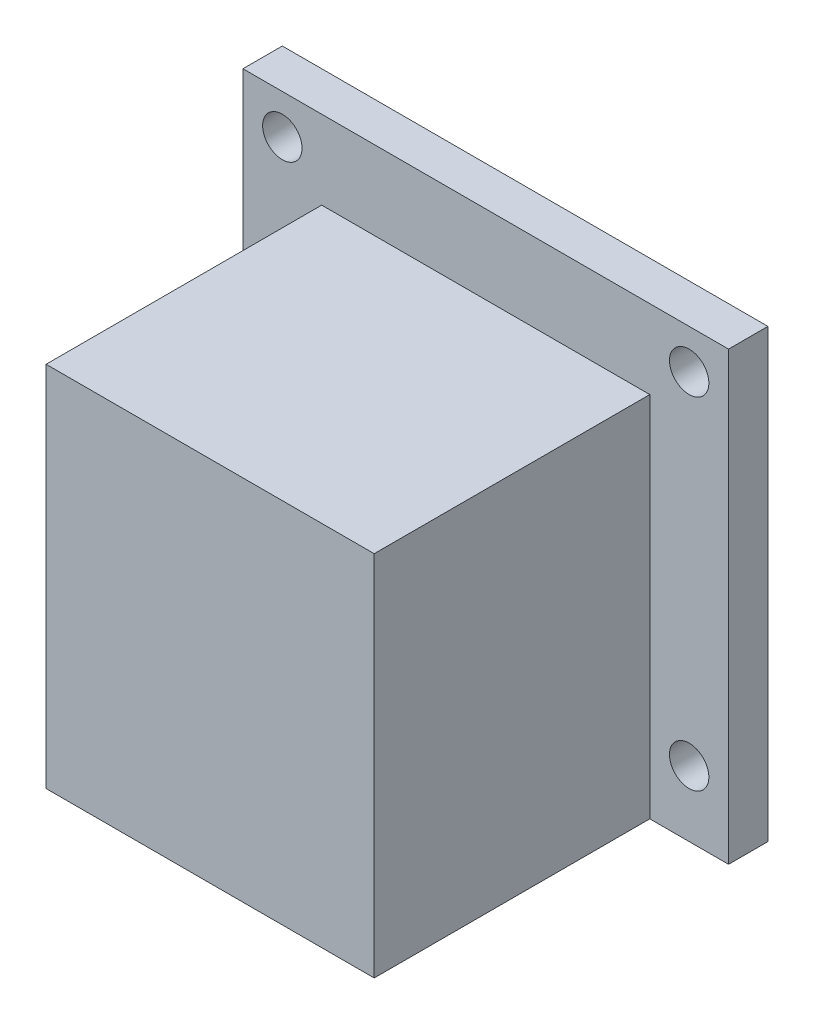
SolidWorks part; units mm, degrees
ref_plane "前视基准面" through (0, 0, 0) normal (0, 0, 1) x (1, 0, 0)
ref_plane "上视基准面" through (0, 0, 0) normal (0, 1, 0) x (1, 0, 0)
ref_plane "右视基准面" through (0, 0, 0) normal (1, 0, 0) x (0, 0, -1)
sketch "草图1" plane through (0, 0, 0) normal (0, 1, 0) x (1, 0, 0)
  line L1 (12.5, -12.5) -> (-12.5, -12.5)
  line L2 (12.5, -12.5) -> (12.5, 12.5)
  line L3 (12.5, 12.5) -> (-12.5, 12.5)
  line L4 (-12.5, -12.5) -> (-12.5, 12.5)
  line L5 (12.5, -12.5) -> (-12.5, 12.5) construction
  line L6 (12.5, 12.5) -> (-12.5, -12.5) construction
  point P0 (0, 0)
  dimension "D1" = 25
  dimension "D2" = 25
extrude "凸台-拉伸1" add sketch "草图1" along normal blind 25
shell "抽壳2" thickness 2 removed face at (0, 12.5, -12.5)
sketch "草图2" plane through (0, 2, 0) normal (0, 1, 0) x (1, 0, 0)
  line L4 (-10.5, 12.5) -> (-10.5, -10.5)
  line L5 (-10.5, -10.5) -> (10.5, -10.5)
  line L6 (10.5, -10.5) -> (10.5, 12.5)
  line L7 (10.5, 12.5) -> (-10.5, 12.5)
  line L8 (-10.5, 12.5) -> (-10.5, -10.5)
  line L9 (-10.5, -10.5) -> (10.5, -10.5)
  line L10 (10.5, -10.5) -> (10.5, 12.5)
  line L11 (10.5, 12.5) -> (-10.5, 12.5)
  dimension "D1" = 0
extrude "切除-拉伸1" cut sketch "草图2" against normal blind 25
sketch "草图3" plane through (0, 25, 0) normal (0, 1, 0) x (1, 0, 0)
  line L4 (-12.5, 12.5) -> (-12.5, -12.5)
  line L5 (-12.5, -12.5) -> (12.5, -12.5)
  line L6 (12.5, -12.5) -> (12.5, 12.5)
  line L7 (12.5, 12.5) -> (-12.5, 12.5)
  line L8 (-12.5, 12.5) -> (-12.5, -12.5)
  line L9 (-12.5, -12.5) -> (12.5, -12.5)
  line L10 (12.5, -12.5) -> (12.5, 12.5)
  line L11 (12.5, 12.5) -> (-12.5, 12.5)
  dimension "D1" = 0
extrude "凸台-拉伸2" add sketch "草图3" along normal blind 3
sketch "草图5" plane through (0, 0, -12.5) normal (0, 0, -1) x (-1, 0, 0)
  line L0 (18.5, 0) -> (18.5, 34)
  line L1 (18.5, 34) -> (-18.5, 34)
  line L2 (-18.5, 34) -> (-18.5, 0)
  line L3 (-18.5, 0) -> (-12.5, 0)
  line L4 (12.5, 0) -> (18.5, 0)
  line L8 (-12.5, 0) -> (-10.5, 0)
  line L9 (-10.5, 0) -> (-10.5, 23)
  line L10 (-10.5, 23) -> (10.5, 23)
  line L11 (10.5, 23) -> (10.5, 0)
  line L12 (10.5, 0) -> (12.5, 0)
  line L13 (12.5, 0) -> (12.5, 28)
  line L14 (12.5, 28) -> (-12.5, 28)
  line L15 (-12.5, 28) -> (-12.5, 0)
  line L21 (12.5, 0) -> (12.5, 28)
  line L22 (12.5, 28) -> (-12.5, 28)
  line L23 (-12.5, 28) -> (-12.5, 0)
  dimension "D1" = 0
  dimension "D2" = 6
extrude "凸台-拉伸3" add sketch "草图5" against normal blind 4
sketch "草图6" plane through (0, 0, -12.5) normal (0, 0, -1) x (-1, 0, 0)
  line L8 (10.5, 0) -> (18.5, 0)
  line L9 (18.5, 0) -> (18.5, 34)
  line L10 (18.5, 34) -> (-18.5, 34)
  line L11 (-18.5, 34) -> (-18.5, 0)
  line L12 (-18.5, 0) -> (-10.5, 0)
  line L13 (-10.5, 0) -> (-10.5, 23)
  line L14 (-10.5, 23) -> (10.5, 23)
  line L15 (10.5, 23) -> (10.5, 0)
  line L16 (10.5, 0) -> (18.5, 0)
  line L17 (18.5, 0) -> (18.5, 34)
  line L18 (18.5, 34) -> (-18.5, 34)
  line L19 (-18.5, 34) -> (-18.5, 0)
  line L20 (-18.5, 0) -> (-10.5, 0)
  line L21 (-10.5, 0) -> (-10.5, 23)
  line L22 (-10.5, 23) -> (10.5, 23)
  line L23 (10.5, 23) -> (10.5, 0)
  dimension "D1" = 0
extrude "切除-拉伸2" cut sketch "草图6" against normal blind 1
sketch "草图7" plane through (0, 0, -11.5) normal (0, 0, -1) x (-1, 0, 0)
  line L0 (-18.5, 34) -> (-18.5, 0) construction
  line L1 (-18.5, 0) -> (-10.5, 0) construction
  line L2 (18.5, 34) -> (-18.5, 34) construction
  line L3 (0, -1000) -> (0, 49000) construction
  circle A0 centre (-15.5, 5) radius 1.5
  circle A1 centre (-15.5, 31) radius 1.5
  circle A2 centre (15.5, 5) radius 1.5
  circle A3 centre (15.5, 31) radius 1.5
  dimension "D1" = 3
  dimension "D6" = 3
  dimension "D2" = 3
  dimension "D3" = 5
  dimension "D4" = 3
  dimension "D5" = 3
extrude "切除-拉伸3" cut sketch "草图7" against normal through all
